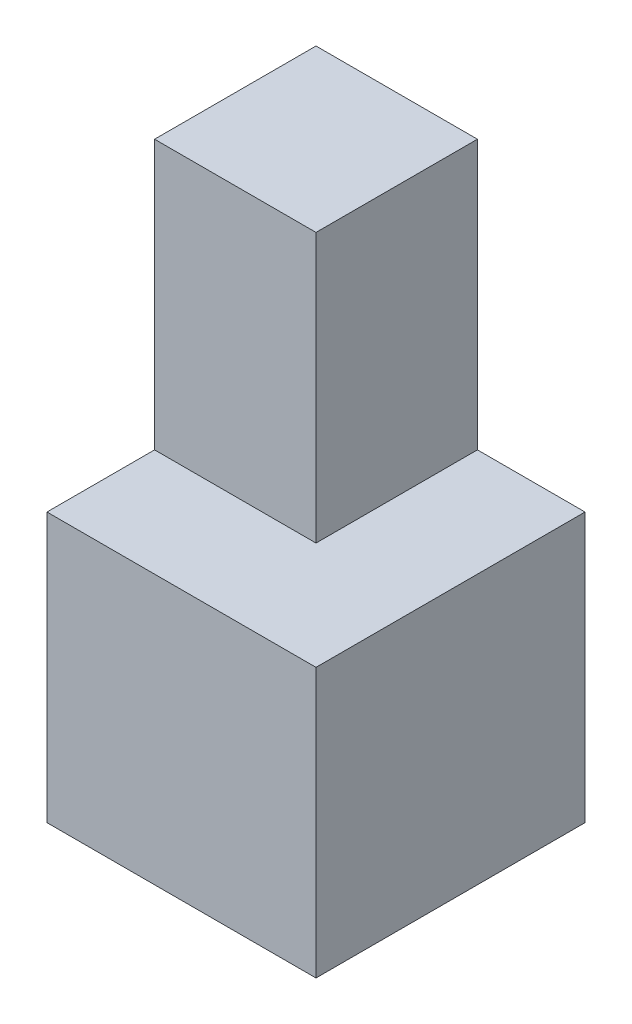
SolidWorks part; units mm, degrees
ref_plane "Front Plane" through (0, 0, 0) normal (0, 0, 1) x (1, 0, 0)
ref_plane "Top Plane" through (0, 0, 0) normal (0, 1, 0) x (1, 0, 0)
ref_plane "Right Plane" through (0, 0, 0) normal (1, 0, 0) x (0, 0, -1)
sketch "Sketch1" plane through (0, 0, 0) normal (0, 1, 0) x (1, 0, 0)
  line L0 (-200, 200) -> (200, -200) construction
  line L1 (-800, 800) -> (200, 800)
  line L2 (-800, 800) -> (-800, -200)
  line L3 (-800, -200) -> (200, -200)
  line L4 (200, 800) -> (200, -200)
  line L5 (-800, 800) -> (200, -200) construction
  line L6 (-800, -200) -> (200, 800) construction
  line L7 (-800, 800) -> (-200, 800)
  line L8 (-800, 800) -> (-800, 200)
  line L9 (-800, 200) -> (-200, 200)
  line L10 (-200, 800) -> (-200, 200)
  point P0 (-300, 300)
  point P9 (0, 0)
  dimension "D1" = 1000
  dimension "D2" = 1000
  dimension "D3" = 400
extrude "Boss-Extrude1" add sketch "Sketch1" against normal blind 1000 contours L1 L10 L9 L2 L3 L4 | L10 L1 L2 L9 region at (-500, 0, -500) region at (-187.5, 0, -187.5)
extrude "Boss-Extrude2" add sketch "Sketch1<3>" along normal blind 1000 contours L10 L1 L2 L9 region at (-500, 0, -500)
sketch "Sketch1<3>" plane through (0, 0, 0) normal (0, 1, 0) x (1, 0, 0) same geometry as "Sketch1"
